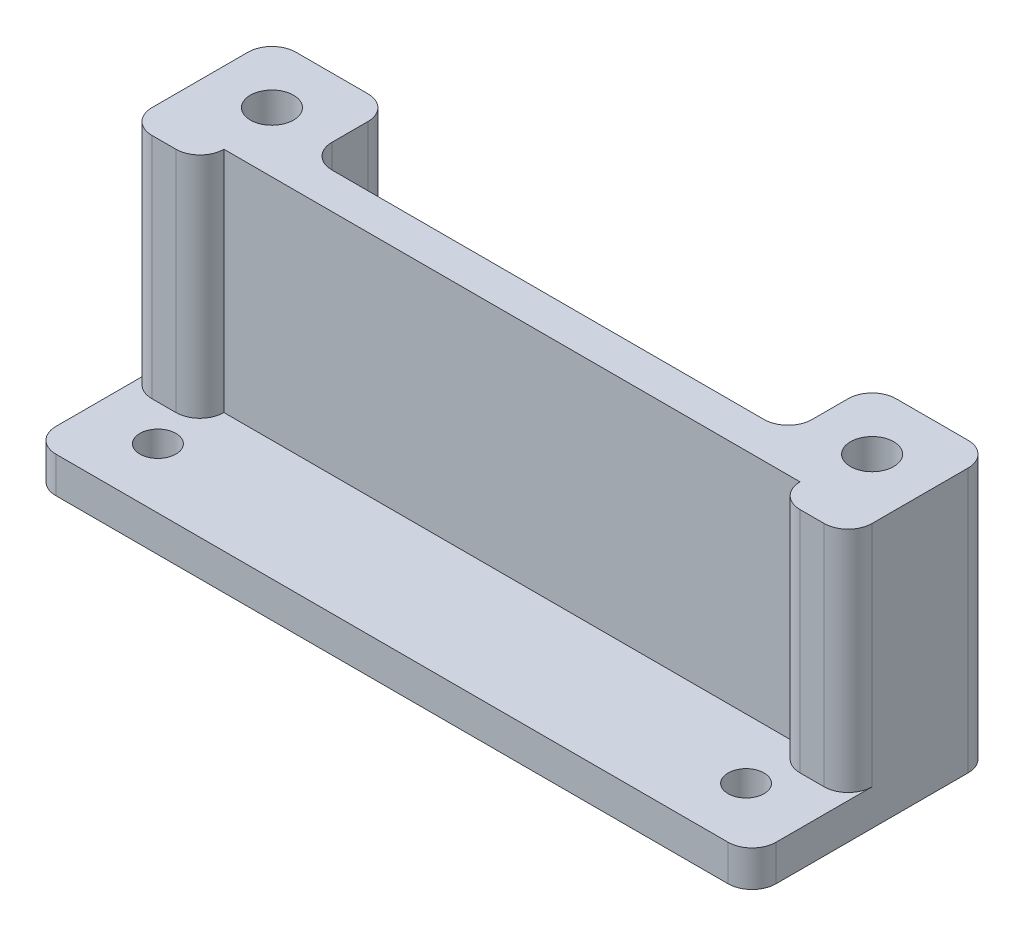
SolidWorks part; units mm, degrees
ref_plane "正面" through (0, 0, 0) normal (0, 0, 1) x (1, 0, 0)
ref_plane "平面" through (0, 0, 0) normal (0, 1, 0) x (1, 0, 0)
ref_plane "右側面" through (0, 0, 0) normal (1, 0, 0) x (0, 0, -1)
sketch "ｽｹｯﾁ1" plane through (0, 0, 0) normal (0, 1, 0) x (1, 0, 0)
  line L0 (2.3806, -6.0448) -> (2.3806, -26.0448) construction
  line L1 (-27.6194, -6.0448) -> (32.3806, -6.0448)
  line L2 (-27.6194, -6.0448) -> (-27.6194, -26.0448)
  line L3 (-27.6194, -26.0448) -> (32.3806, -26.0448)
  line L4 (32.3806, -6.0448) -> (32.3806, -26.0448)
  line L5 (-34.2761, -21.0448) -> (39.7537, -21.0448) construction
  line L6 (-27.6194, -11.0448) -> (32.3806, -11.0448) construction
  circle A0 centre (-22.1194, -21.0448) radius 1.5
  circle A1 centre (26.8806, -21.0448) radius 1.5
  circle A4 centre (-22.6194, -11.0448) radius 1.8
  circle A5 centre (27.3806, -11.0448) radius 1.8
  point P0 (0.9701, -10.2239)
  dimension "D5" = 3
  dimension "D6" = 3
  dimension "D8" = 3.6
  dimension "D1" = 30
  dimension "D2" = 24.5
  dimension "D3" = 24.5
  dimension "D4" = 30
  dimension "D7" = 20
  dimension "D9" = 5
  dimension "D10" = 25
  dimension "D11" = 25
  dimension "D12" = 10
extrude "ﾎﾞｽ - 押し出し1" add sketch "ｽｹｯﾁ1" along normal blind 3
sketch "ｽｹｯﾁ7" plane through (0, 3, 0) normal (0, 1, 0) x (1, 0, 0)
  line L0 (-27.6194, -6.0448) -> (-27.6194, -26.0448) construction
  line L1 (-27.6194, -16.0448) -> (32.3806, -16.0448)
  line L2 (-27.6194, -16.0448) -> (-27.6194, -6.0448)
  line L3 (-27.6194, -6.0448) -> (32.3806, -6.0448)
  line L4 (32.3806, -16.0448) -> (32.3806, -6.0448)
  line L5 (-22.1194, -21.0448) -> (26.8806, -21.0448) construction
  line L6 (2.3806, -6.0448) -> (2.3806, -26.0448) construction
  line L7 (-27.6194, -26.0448) -> (32.3806, -26.0448) construction
  dimension "D1" = 5
extrude "ﾎﾞｽ - 押し出し3" add sketch "ｽｹｯﾁ7" along normal blind 19
sketch "ｽｹｯﾁ8" plane through (0, 3, 0) normal (0, -1, 0) x (1, 0, 0)
  circle A0 centre (27.3806, 11.0448) radius 1.8
  circle A1 centre (-22.6194, 11.0448) radius 1.8
extrude "ｶｯﾄ - 押し出し3" cut sketch "ｽｹｯﾁ8" against normal through all
sketch "ｽｹｯﾁ9" plane through (0, 0, 16.0448) normal (0, 0, 1) x (1, 0, 0)
  line L0 (2.3806, 0) -> (2.3806, 22) construction
  line L1 (-27.6194, 0) -> (32.3806, 0) construction
  line L2 (-27.6194, 22) -> (32.3806, 22) construction
  line L3 (-27.6194, 3) -> (32.3806, 3) construction
  line L4 (32.3806, 22) -> (26.3806, 22)
  line L5 (32.3806, 22) -> (32.3806, 3)
  line L6 (32.3806, 3) -> (26.3806, 3)
  line L7 (26.3806, 22) -> (26.3806, 3)
  line L9 (-27.6194, 22) -> (-21.6194, 22)
  line L10 (-27.6194, 22) -> (-27.6194, 3)
  line L11 (-27.6194, 3) -> (-21.6194, 3)
  line L12 (-21.6194, 22) -> (-21.6194, 3)
  dimension "D1" = 24
  dimension "D2" = 24
extrude "ﾎﾞｽ - 押し出し4" add sketch "ｽｹｯﾁ9" along normal blind 2
sketch "ｽｹｯﾁ10" plane through (0, 22, 0) normal (0, 1, 0) x (1, 0, 0)
  line L0 (2.3806, -16.0448) -> (2.3806, -6.0448) construction
  line L1 (-21.6194, -16.0448) -> (26.3806, -16.0448) construction
  line L2 (32.3806, -6.0448) -> (-27.6194, -6.0448) construction
  line L3 (32.3806, -18.0448) -> (32.3806, -6.0448) construction
  line L4 (-17.6194, -6.0448) -> (22.3806, -6.0448)
  line L5 (-17.6194, -6.0448) -> (-17.6194, -13.0448)
  line L6 (-17.6194, -13.0448) -> (22.3806, -13.0448)
  line L7 (22.3806, -6.0448) -> (22.3806, -13.0448)
  line L8 (-17.6194, -6.0448) -> (22.3806, -13.0448) construction
  line L9 (-17.6194, -13.0448) -> (22.3806, -6.0448) construction
  point P6 (2.3806, -9.5448)
  dimension "D1" = 3
  dimension "D2" = 10
extrude "ｶｯﾄ - 押し出し4" cut sketch "ｽｹｯﾁ10" against normal through all
fillet "ﾌｨﾚｯﾄ2" radius 2 12 edges at (-21.6194, 12.5, 18.0448) (26.3806, 12.5, 18.0448) (32.3806, 12.5, 18.0448) (-27.6194, 12.5, 18.0448) (-27.6194, 1.5, 26.0448) (32.3806, 1.5, 26.0448) (-27.6194, 11, 6.0448) (-17.6194, 11, 6.0448) (22.3806, 11, 6.0448) (32.3806, 11, 6.0448) (-17.6194, 11, 13.0448) (22.3806, 11, 13.0448)
